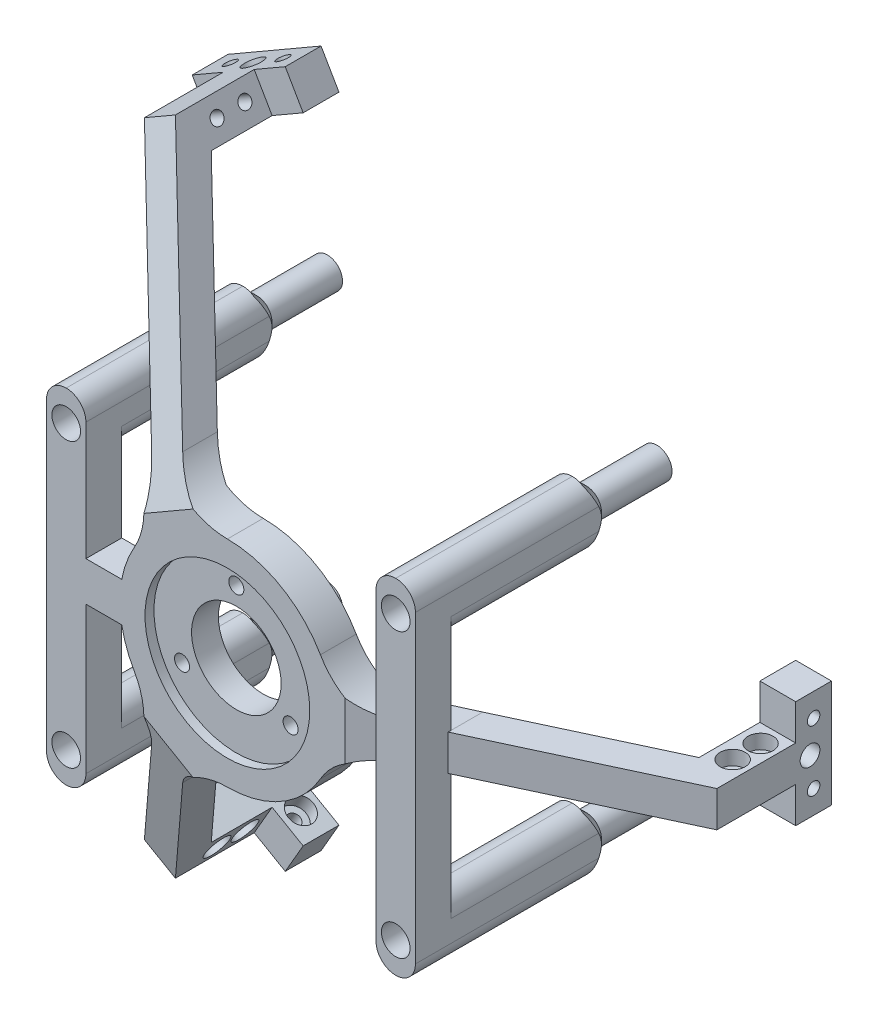
SolidWorks part; units mm, degrees
ref_plane "Plan de face" through (0, 0, 0) normal (0, 0, 1) x (1, 0, 0)
ref_plane "Plan de dessus" through (0, 0, 0) normal (0, 1, 0) x (1, 0, 0)
ref_plane "Plan de droite" through (0, 0, 0) normal (1, 0, 0) x (0, 0, -1)
sketch "Esquisse1" plane through (0, 0, 0) normal (0, 0, 1) x (1, 0, 0)
  line L0 (0, 0) -> (93.67, 0) construction
  line L1 (93.67, 15) -> (103.67, 15)
  line L2 (93.67, 15) -> (93.67, -15)
  line L3 (93.67, -15) -> (103.67, -15)
  line L4 (103.67, 15) -> (103.67, -15)
  line L5 (-33.8446, -88.6206) -> (-59.8254, -73.6206)
  line L6 (-33.8446, -88.6206) -> (-38.8446, -97.2809)
  line L7 (-38.8446, -97.2809) -> (-64.8254, -82.2809)
  line L8 (-59.8254, -73.6206) -> (-64.8254, -82.2809)
  line L9 (-59.8254, 73.6206) -> (-33.8446, 88.6206)
  line L10 (-59.8254, 73.6206) -> (-64.8254, 82.2809)
  line L11 (-64.8254, 82.2809) -> (-38.8446, 97.2809)
  line L12 (-33.8446, 88.6206) -> (-38.8446, 97.2809)
  point P17 (0, 0)
  dimension "D1" = 30
  dimension "D2" = 10
  dimension "D3" = 93.67
  dimension "D4" = 3
extrude "Boss.-Extru.1" add sketch "Esquisse1" along normal blind 10
sketch "Esquisse2" plane through (0, 0, 10) normal (0, 0, 1) x (1, 0, 0)
  line L0 (-57.0272, 86.7831) -> (-46.3532, 92.9458)
  line L1 (-38.8446, 97.2809) -> (-64.8254, 82.2809) construction
  line L2 (93.67, 15) -> (93.67, -15) construction
  line L3 (93.67, 5) -> (103.67, 5)
  line L4 (93.67, 5) -> (93.67, -5)
  line L5 (93.67, -5) -> (103.67, -5)
  line L6 (103.67, 5) -> (103.67, -5)
  line L7 (103.67, -15) -> (103.67, 15) construction
  line L8 (-42.5049, -83.6206) -> (-51.1651, -78.6206)
  line L9 (-42.5049, -83.6206) -> (-47.5049, -92.2809)
  line L10 (-47.5049, -92.2809) -> (-56.1651, -87.2809)
  line L11 (-51.1651, -78.6206) -> (-56.1651, -87.2809)
  line L12 (-51.1651, 78.6206) -> (-42.5049, 83.6206)
  line L13 (-51.1651, 78.6206) -> (-56.1651, 87.2809)
  line L14 (-56.1651, 87.2809) -> (-47.5049, 92.2809)
  line L15 (-42.5049, 83.6206) -> (-47.5049, 92.2809)
  point P12 (93.67, 0)
  point P13 (93.67, 0)
  point P24 (0, 0)
  line M6 (-59.8254, 73.6206) -> (-33.8446, 88.6206)
  dimension "D1" = 3
extrude "Boss.-Extru.2" add sketch "Esquisse2" along normal blind 45 contours L15 L0 L13 M6 | L6 L3 L4 L5 | L8 L11 L10 L9 region at (-49.335, 85.4507, 10) region at (98.67, 0, 10) region at (-49.335, -85.4507, 10)
sketch "Esquisse3" plane through (0, 0, 55) normal (0, 0, 1) x (1, 0, 0)
  line L0 (103.67, 5) -> (103.67, -5) construction
  line L1 (-47.5049, -92.2809) -> (-56.1651, -87.2809) construction
  line L2 (-47.5049, 92.2809) -> (-56.1651, 87.2809) construction
  line L3 (103.67, 5) -> (103.67, -5)
  line L4 (-47.5049, -92.2809) -> (-56.1651, -87.2809)
  line L5 (-47.5049, 92.2809) -> (-56.1651, 87.2809)
  line L6 (-56.1651, -87.2809) -> (-19.1203, -23.1174)
  line L7 (-47.5049, -92.2809) -> (-10.4601, -28.1174)
  line L8 (103.67, -5) -> (29.5804, -5)
  line L9 (103.67, 5) -> (29.5804, 5)
  line L10 (-56.1651, 87.2809) -> (-19.1203, 23.1174)
  line L11 (-47.5049, 92.2809) -> (-10.4601, 28.1174)
  line L12 (-51.1651, -78.6206) -> (-56.1651, -87.2809) construction
  line L13 (-42.5049, -83.6206) -> (-47.5049, -92.2809) construction
  line L14 (93.67, -5) -> (103.67, -5) construction
  line L15 (93.67, 5) -> (103.67, 5) construction
  line L16 (-51.1651, 78.6206) -> (-56.1651, 87.2809) construction
  line L17 (-42.5049, 83.6206) -> (-47.5049, 92.2809) construction
  arc A0 (-19.1203, -23.1174) -> (-19.1203, 23.1174) centre (0, 0) cw
  arc A1 (-10.4601, 28.1174) -> (29.5804, 5) centre (0, 0) cw
  arc A2 (29.5804, -5) -> (-10.4601, -28.1174) centre (0, 0) cw
  dimension "D1" = 30
extrude "Boss.-Extru.3" add sketch "Esquisse3" along normal blind 10
chamfer "Chanfrein1" distance 28 angle 65 3 edges at (93.67, 0, 55) (-46.835, -81.1206, 55) (-46.835, 81.1206, 55) first distance on face at (93.67, 0, 18.75) first distance on face at (-46.835, -81.1206, 18.75) first distance on face at (-46.835, 81.1206, 18.75)
chamfer "Chanfrein2" distance 33 angle 65 3 edges at (-51.835, -89.7809, 65) (-51.835, 89.7809, 65) (103.67, 0, 65) first distance on face at (-51.835, -89.7809, 21.25) first distance on face at (-51.835, 89.7809, 21.25) first distance on face at (103.67, 0, 21.25)
fillet "Congé1" radius 20 6 edges at (29.5804, -5, 60) (-10.4601, -28.1174, 60) (-19.1203, -23.1174, 60) (-19.1203, 23.1174, 60) (29.5804, 5, 60) (-10.4601, 28.1174, 60)
sketch "Esquisse4" plane through (0, 0, 65) normal (0, 0, 1) x (1, 0, 0)
  circle A0 centre (0, 0) radius 12.5
  dimension "D1" = 25
extrude "Enlèv. mat.-Extru.1" cut sketch "Esquisse4" against normal up to next
sketch "Esquisse5" plane through (0, 0, 65) normal (0, 0, 1) x (1, 0, 0)
  circle A0 centre (0, 0) radius 23
  dimension "D1" = 46
extrude "Enlèv. mat.-Extru.2" cut sketch "Esquisse5" against normal blind 2.5
sketch "Esquisse6" plane through (0, 0, 62.5) normal (0, 0, 1) x (1, 0, 0)
  line L0 (0, 17.5) -> (0, 0) construction
  circle A0 centre (0, 17.5) radius 2.1
  circle A1 centre (15.1554, -8.75) radius 2.1
  circle A2 centre (-15.1554, -8.75) radius 2.1
  point P10 (0, 0)
  dimension "D2" = 4.2
  dimension "D1" = 17.5
  dimension "D3" = 3
extrude "Enlèv. mat.-Extru.3" cut sketch "Esquisse6" against normal up to next
sketch "Esquisse7" plane through (0, 0, 55) normal (0, 0, -1) x (-1, 0, 0)
  line L0 (0, 0) -> (39.5, 0) construction
  line L1 (-41.5, -52) -> (-52.5, -52)
  line L2 (-41.5, -52) -> (-41.5, 44)
  line L3 (-41.5, 44) -> (-52.5, 44)
  line L4 (-52.5, -52) -> (-52.5, 44)
  line L5 (50.5, -52) -> (39.5, -52)
  line L6 (39.5, -52) -> (39.5, -5.5)
  line L7 (39.5, -5.5) -> (29.4915, -5.5)
  line L8 (50.5, -52) -> (50.5, 44)
  line L9 (50.5, 44) -> (39.5, 44)
  line L10 (39.5, 44) -> (39.5, 5.5)
  line L11 (39.5, 5.5) -> (29.4915, 5.5)
  line L12 (39.5, -5.5) -> (39.5, 5.5) construction
  arc A0 (25.9808, -15) -> (25.9808, 15) centre (0, 0) ccw construction
  arc A1 (29.4915, -5.5) -> (29.4915, 5.5) centre (0, 0) ccw
  point P7 (-47, 44)
  point P21 (45, 44)
  point P22 (39.5, 0)
  dimension "D1" = 11
  dimension "D2" = 52
  dimension "D3" = 96
  dimension "D4" = 47
  dimension "D5" = 92
extrude "Boss.-Extru.4" add sketch "Esquisse7" along normal blind 39.3 and the other way up to surface (10 mm away) other way up to face at (23, 0, 65)
sketch "Esquisse8" plane through (0, 0, 15.7) normal (0, 0, -1) x (-1, 0, 0)
  line L0 (-52.5, -4) -> (50.5, -4) construction
  line L1 (-52.5, 44) -> (-52.5, -52) construction
  line L2 (50.5, -52) -> (50.5, 44) construction
  line L3 (45, 35.5) -> (-47, 35.5) construction
  line L4 (-1, -4) -> (-1, 35.5) construction
  line L5 (-52.5, -52) -> (-41.5, -52) construction
  circle A0 centre (45, 35.5) radius 4
  circle A1 centre (-47, 35.5) radius 4
  circle A2 centre (-47, -43.5) radius 4
  circle A3 centre (45, -43.5) radius 4
  dimension "D4" = 8
  dimension "D1" = 92
  dimension "D2" = 79
  dimension "D3" = 8.5
extrude "Enlèv. mat.-Extru.4" cut sketch "Esquisse8" against normal up to next
sketch "Esquisse18" plane through (0, 0, 15.7) normal (0, 0, -1) x (-1, 0, 0)
  circle A0 centre (-47, 35.5) radius 4.25
  circle A1 centre (-47, -43.5) radius 4.25
  circle A2 centre (45, 35.5) radius 4.25
  circle A3 centre (45, -43.5) radius 4.25
  circle A12 centre (45, 35.5) radius 2.5
  circle A13 centre (-47, 35.5) radius 2.5
  circle A14 centre (-47, -43.5) radius 2.5
  circle A15 centre (45, -43.5) radius 2.5
  dimension "D1" = 8.5
  dimension "D2" = 5
extrude "Boss.-Extru.6" add sketch "Esquisse18" along normal blind 15
chamfer "Chanfrein3" distance 3.9 angle 45 4 edges at (42.75, -43.5, 15.7) (42.75, 35.5, 15.7) (-49.25, -43.5, 15.7) (-49.25, 35.5, 15.7)
sketch "Esquisse19" plane through (0, 0, 0.7) normal (0, 0, -1) x (-1, 0, 0)
  circle A0 centre (-47, -43.5) radius 4.25 construction
  circle A1 centre (-47, 35.5) radius 4.25 construction
  circle A2 centre (45, 35.5) radius 4.25 construction
  circle A3 centre (45, -43.5) radius 4.25 construction
  circle A4 centre (-47, -43.5) radius 4.25
  circle A5 centre (-47, 35.5) radius 4.25
  circle A6 centre (45, 35.5) radius 4.25
  circle A7 centre (45, -43.5) radius 4.25
  circle A8 centre (-47, -43.5) radius 1.5
  circle A9 centre (-47, 35.5) radius 1.5
  circle A10 centre (45, 35.5) radius 1.5
  circle A11 centre (45, -43.5) radius 1.5
  dimension "D1" = 3
extrude "Boss.-Extru.7" add sketch "Esquisse19" along normal blind 8.6
sketch "Esquisse10" plane through (0, 0, 15.7) normal (0, 0, -1) x (-1, 0, 0)
  line L6 (50.5, -52) -> (50.5, -49.5144) construction
  line L7 (50.5, -35) -> (29.4915, -35)
  line L8 (50.5, -35) -> (50.5, 27)
  line L9 (50.5, 27) -> (29.4915, 27)
  line L10 (29.4915, -35) -> (29.4915, 27)
  line L11 (45, 35.5) -> (45, 27) construction
  line L12 (45, -43.5) -> (45, -35) construction
  line L13 (-52.5, 44) -> (-52.5, 41.5144) construction
  line L14 (-52.5, 27) -> (-41.5, 27)
  line L15 (-52.5, 27) -> (-52.5, -35)
  line L16 (-52.5, -35) -> (-41.5, -35)
  line L17 (-41.5, 27) -> (-41.5, -35)
  line L18 (-41.5, -52) -> (-41.5, -49.5144) construction
  dimension "D1" = 8.5
extrude "Enlèv. mat.-Extru.6" cut sketch "Esquisse10" against normal up to surface (39.3 mm away) up to face at (-2.1, 17.5, 55)
sketch "Esquisse17" plane through (0, 0, 55) normal (0, 0, -1) x (-1, 0, 0)
  line L0 (-41.5, -5.0813) -> (-52.5, -5)
  line L1 (-52.5, -5) -> (-52.5, 5)
  line L2 (-52.5, 5) -> (-41.5, 5.0813)
  line L3 (-41.5, 5.0813) -> (-41.5, -5.0813)
extrude "Boss.-Extru.5" add sketch "Esquisse17" along normal up to surface (8.8021 mm away) contours L3 L0 L1 L2 up to face at (73.085, 0, 36.5989)
fillet "Congé2" radius 5.5 16 edges at (-50.5, 44, 40.35) (-39.5, 44, 40.35) (41.5, 44, 40.35) (52.5, 44, 40.35) (-50.5, -52, 40.35) (-39.5, -52, 40.35) (52.5, -52, 40.35) (41.5, -52, 40.35) (-50.5, 27, 35.35) (-39.5, 27, 35.35) (-50.5, -35, 35.35) (-39.5, -35, 35.35) (41.5, -35, 35.35) (52.5, -35, 35.35) (41.5, 27, 35.35) (52.5, 27, 35.35)
sketch "Esquisse11" plane through (4.3301, -2.5, 0) normal (0.866, -0.5, 0) x (0, 0, -1)
  line L0 (-27, -93.67) -> (-10, -93.67) construction
  line L1 (-10, -93.67) -> (-10, -103.67) construction
  circle A0 centre (-15, -98.86) radius 1.75
  circle A1 centre (-22.78, -98.86) radius 1.75
  dimension "D4" = 3.5
  dimension "D1" = 5.19
  dimension "D2" = 5
  dimension "D3" = 7.78
extrude "Enlèv. mat.-Extru.7" cut sketch "Esquisse11" against normal up to next
sketch "Esquisse12" plane through (4.3301, -2.5, 0) normal (0.866, -0.5, 0) x (0, 0, -1)
  circle A0 centre (-15, -98.86) radius 3.5
  circle A1 centre (-22.78, -98.86) radius 3.5
  dimension "D1" = 7
extrude "Enlèv. mat.-Extru.8" cut sketch "Esquisse12" against normal blind 4
sketch "Esquisse13" plane through (-46.835, -81.1206, 0) normal (0.5, 0.866, 0) x (0.866, -0.5, 0)
  line L0 (-15, -10) -> (-15, 0) construction
  line L1 (-15, -5) -> (-8.5, -5) construction
  line L2 (15, -5) -> (8.5, -5) construction
  line L3 (15, -10) -> (15, 0) construction
  circle A0 centre (-8.5, -5) radius 1.75
  circle A1 centre (8.5, -5) radius 1.75
  dimension "D2" = 3.5
  dimension "D1" = 6.5
extrude "Enlèv. mat.-Extru.9" cut sketch "Esquisse13" against normal up to next
sketch "Esquisse14" plane through (-46.835, -81.1206, 0) normal (0.5, 0.866, 0) x (0.866, -0.5, 0)
  circle A0 centre (-8.5, -5) radius 3.5
  circle A1 centre (8.5, -5) radius 3.5
  dimension "D1" = 7
extrude "Enlèv. mat.-Extru.10" cut sketch "Esquisse14" against normal blind 4
sketch "Esquisse15" plane through (-46.835, -81.1206, 0) normal (0.5, 0.866, 0) x (0.866, -0.5, 0)
  line L0 (15, 0) -> (-15, 0) construction
  line L1 (-15, -10) -> (-15, 0) construction
  circle A0 centre (0, -6) radius 2.75
  point P5 (0, 0)
  point P8 (-15, -5)
  dimension "D1" = 5.5
  dimension "D2" = 1
extrude "Enlèv. mat.-Extru.11" cut sketch "Esquisse15" against normal up to next
pattern_circular "Répétition circulaire1" count 3 over 360 about axis through (0, 0, -0.001) along (0, 0, 1) of "Enlèv. mat.-Extru.7", "Enlèv. mat.-Extru.11", "Enlèv. mat.-Extru.10", "Enlèv. mat.-Extru.9", "Enlèv. mat.-Extru.8" reverse direction yes
